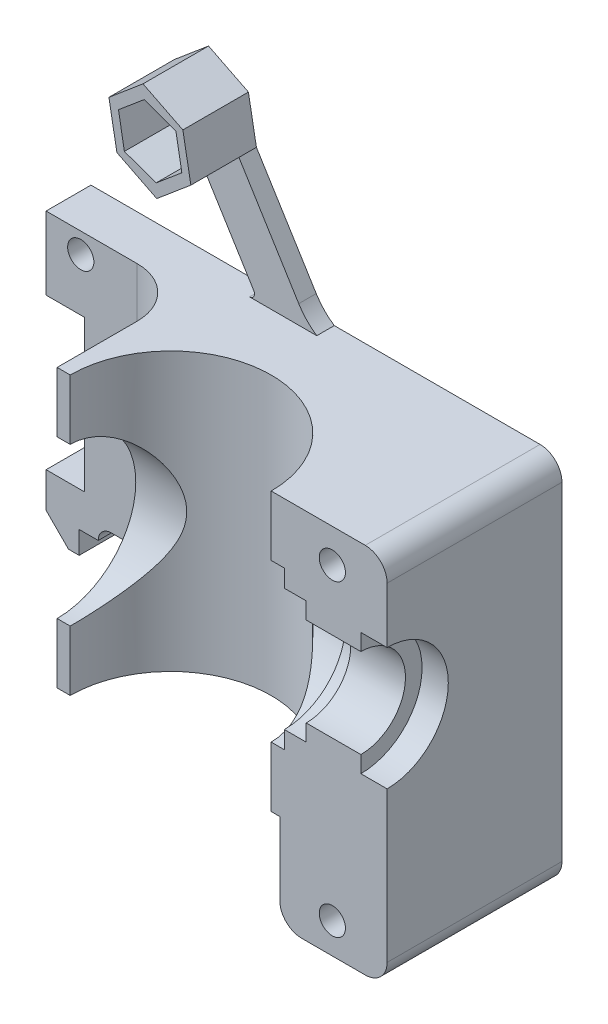
SolidWorks part; units mm, degrees
ref_plane "Front Plane" through (0, 0, 0) normal (0, 0, 1) x (1, 0, 0)
ref_plane "Top Plane" through (0, 0, 0) normal (0, 1, 0) x (1, 0, 0)
ref_plane "Right Plane" through (0, 0, 0) normal (1, 0, 0) x (0, 0, -1)
sketch "Sketch4" plane through (0, 0, 0) normal (0, 0, 1) x (1, 0, 0)
  line L0 (935.8201, 667.6975) -> (1296.762, 667.6975)
  line L1 (1321.762, 642.6975) -> (1321.762, 266.9066)
  line L2 (1296.762, 241.9066) -> (1223.9504, 241.9066)
  line L3 (1198.9504, 266.9066) -> (1198.9504, 350.067)
  line L4 (1198.9504, 350.067) -> (898.9504, 350.067)
  line L5 (898.9504, 350.067) -> (898.9504, 371.0706)
  line L6 (883.9504, 386.0706) -> (857.5132, 386.0706)
  line L7 (842.5132, 371.0706) -> (840.666, 371.0706)
  line L8 (840.666, 371.0706) -> (840.666, 345.3724)
  line L9 (808.5784, 345.3724) -> (782.8801, 371.0706)
  line L10 (782.8801, 371.0706) -> (782.8801, 411.3747)
  line L11 (782.8801, 411.3747) -> (826.6656, 411.3747)
  line L12 (826.6656, 411.3747) -> (826.6656, 584.3337)
  line L13 (826.6656, 584.3337) -> (782.8801, 584.3337)
  line L14 (782.8801, 584.3337) -> (782.8801, 642.6975)
  line L15 (807.8801, 667.6975) -> (935.8201, 667.6975)
  line L16 (808.5784, 345.3724) -> (840.666, 345.3724)
  line L17 (935.8201, 667.6975) -> (984.3079, 667.6975)
  line L18 (988.8546, 676.9168) -> (933.1895, 766.9852)
  line L19 (933.1895, 766.9852) -> (887.5804, 789.8065)
  line L20 (887.5804, 789.8065) -> (878.419, 839.9769)
  line L21 (878.419, 839.9769) -> (917.4331, 872.8235)
  line L22 (917.4331, 872.8235) -> (963.0422, 850.0022)
  line L23 (963.0422, 850.0022) -> (972.2036, 799.8318)
  line L24 (972.2036, 799.8318) -> (1040.632, 689.1121)
  line L25 (933.1895, 766.9852) -> (972.2036, 799.8318)
  arc A0 (1296.762, 667.6975) -> (1321.762, 642.6975) centre (1296.762, 642.6975) cw
  arc A1 (1321.762, 266.9066) -> (1296.762, 241.9066) centre (1296.762, 266.9066) cw
  arc A2 (1223.9504, 241.9066) -> (1198.9504, 266.9066) centre (1223.9504, 266.9066) cw
  arc A3 (898.9504, 371.0706) -> (883.9504, 386.0706) centre (883.9504, 371.0706) ccw
  arc A4 (857.5132, 386.0706) -> (842.5132, 371.0706) centre (857.5132, 371.0706) ccw
  arc A5 (782.8801, 642.6975) -> (807.8801, 667.6975) centre (807.8801, 642.6975) cw
  arc A6 (984.3079, 667.6975) -> (988.8546, 676.9168) centre (984.3079, 673.4283) ccw
  arc A7 (1040.632, 689.1121) -> (1061.2833, 667.6975) centre (1100.3012, 725.9895) ccw
  dimension "D6" = 25
  dimension "D7" = 25
  dimension "D8" = 15
  dimension "D9" = 15
  dimension "D10" = 25
  dimension "D11" = 25
  dimension "D1" = 51
  dimension "D2" = 51
  dimension "D3" = 51
  dimension "D4" = 51
  dimension "D5" = 51
  dimension "D12" = 300
extrude "Boss-Extrude2" add sketch "Sketch4" along normal blind 20 contours A7 L24 L23 L22 L21 L20 L19 L18 A6 L0 region at (990.055, 725.3838, 0)
extrude "Boss-Extrude3" add sketch "Sketch4<4>" along normal blind 200 contours A5 L14 L13 L12 L11 L10 L9 L16 L8 L7 A4 L6 A3 L5 L4 L3 A2 L2 A1 L1 A0 L0 L15 region at (1080.7929, 494.951, 0)
sketch "Sketch4<4>" plane through (0, 0, 0) normal (0, 0, 1) x (1, 0, 0) same geometry as "Sketch4"
extrude "Boss-Extrude4" add sketch "Sketch4<5>" along normal blind 75 contours L19 L25 L23 L22 L21 L20 region at (925.3113, 819.9043, 0)
sketch "Sketch4<5>" plane through (0, 0, 0) normal (0, 0, 1) x (1, 0, 0) same geometry as "Sketch4"
sketch "Sketch6" plane through (0, 667.6975, 0) normal (0, 1, 0) x (1, 0, 0)
  line L0 (807.8801, -200) -> (1296.762, -200) construction
  line L1 (959.1109, -200) -> (1189.1109, -200)
  line L2 (944.1721, -200) -> (944.1721, -108.4769)
  line L3 (887.0237, -51.3284) -> (741.8117, -51.3284)
  line L4 (741.8117, -51.3284) -> (741.8117, -200)
  line L5 (741.8117, -200) -> (944.1721, -200)
  circle A0 centre (1074.1109, -200) radius 115
  arc A1 (944.1721, -108.4769) -> (887.0237, -51.3284) centre (887.0237, -108.4769) ccw
  line M6 (807.8801, 0) -> (807.8801, -200)
  line M7 (807.8801, -200) -> (1296.762, -200)
  dimension "D1" = 230
extrude "Cut-Extrude2" cut sketch "Sketch6" against normal through all contours L2 A1 L3 M6 M7 | L4 L5 L3 M6 | A0 M7 region at (1074.1109, 667.6975, 151.1925) region at (874.0419, 667.6975, 127.8702) region at (774.8459, 667.6975, 125.6642)
sketch "Sketch9" plane through (944.1721, 0, 0) normal (-1, 0, 0) x (0, 0, 1)
  line L0 (200, 350.067) -> (200, 667.6975) construction
  circle A0 centre (200, 508.8822) radius 90
  dimension "D1" = 180
extrude "Cut-Extrude4" cut sketch "Sketch9" against normal blind 260
sketch "Sketch10" plane through (1204.1721, 0, 0) normal (-1, 0, 0) x (0, 0, 1)
  line L0 (200, 598.8822) -> (200, 418.8822) construction
  circle A0 centre (200, 508.8822) radius 70
  dimension "D1" = 140
extrude "Cut-Extrude5" cut sketch "Sketch10" against normal blind 25
sketch "Sketch11" plane through (1229.1721, 0, 0) normal (-1, 0, 0) x (0, 0, 1)
  line L0 (200, 578.8822) -> (200, 438.8822) construction
  circle A0 centre (200, 508.8822) radius 51
  dimension "D1" = 102
extrude "Cut-Extrude6" cut sketch "Sketch11" against normal blind 360
sketch "Sketch12" plane through (1321.762, 0, 0) normal (1, 0, 0) x (0, 0, -1)
  circle A0 centre (-200, 508.8822) radius 70
  dimension "D1" = 140
extrude "Cut-Extrude7" cut sketch "Sketch12" against normal blind 30
sketch "Sketch13" plane through (0, 0, 51.3284) normal (0, 0, 1) x (1, 0, 0)
  circle A0 centre (822.5387, 644.3796) radius 15
  dimension "D1" = 30
extrude "Cut-Extrude8" cut sketch "Sketch13" against normal through all
sketch "Sketch14" plane through (0, 0, 51.3284) normal (0, 0, 1) x (1, 0, 0)
  line L0 (807.8801, 667.6975) -> (782.8801, 667.6975)
  line L1 (782.8801, 667.6975) -> (782.8801, 642.6975)
  arc A0 (782.8801, 642.6975) -> (807.8801, 667.6975) centre (807.8801, 642.6975) cw
extrude "Boss-Extrude5" add sketch "Sketch14" against normal up to surface (51.3284 mm away) up to face at (837.5387, 644.3796, 0)
sketch "Sketch15" plane through (0, 0, 200) normal (0, 0, 1) x (1, 0, 0)
  circle A0 centre (1259.0867, 629.3637) radius 15
  circle A1 centre (1259.0867, 276.9075) radius 15
  dimension "D1" = 30
  dimension "D2" = 30
extrude "Cut-Extrude9" cut sketch "Sketch15" against normal through all
sketch "Sketch16" plane through (0, 0, 75) normal (0, 0, 1) x (1, 0, 0)
  line L1 (955.131, 844.8485) -> (918.8964, 857.9933)
  line L2 (918.8964, 857.9933) -> (889.3953, 833.1856)
  line L3 (889.3953, 833.1856) -> (896.1289, 795.2331)
  line L4 (896.1289, 795.2331) -> (932.3635, 782.0882)
  line L5 (932.3635, 782.0882) -> (961.8646, 806.896)
  line L6 (961.8646, 806.896) -> (955.131, 844.8485)
  circle A0 centre (925.63, 820.0408) radius 33.3812 construction
extrude "Cut-Extrude10" cut sketch "Sketch16" against normal blind 60
sketch "Sketch17" plane through (0, 0, 15) normal (0, 0, 1) x (1, 0, 0)
  circle A0 centre (925.63, 820.0408) radius 20
  dimension "D1" = 40
extrude "Cut-Extrude11" cut sketch "Sketch17" against normal through all
sketch "Sketch18" plane through (0, 0, 51.3284) normal (0, 0, 1) x (1, 0, 0)
  line L0 (840.666, 371.0706) -> (820.7166, 371.0706)
  line L1 (820.7166, 371.0706) -> (820.7166, 345.3724)
  line L2 (840.666, 345.3724) -> (808.5784, 345.3724) construction
  line L3 (820.7166, 345.3724) -> (840.666, 345.3724)
  line L4 (840.666, 345.3724) -> (840.666, 371.0706)
extrude "Cut-Extrude12" cut sketch "Sketch18" against normal through all
